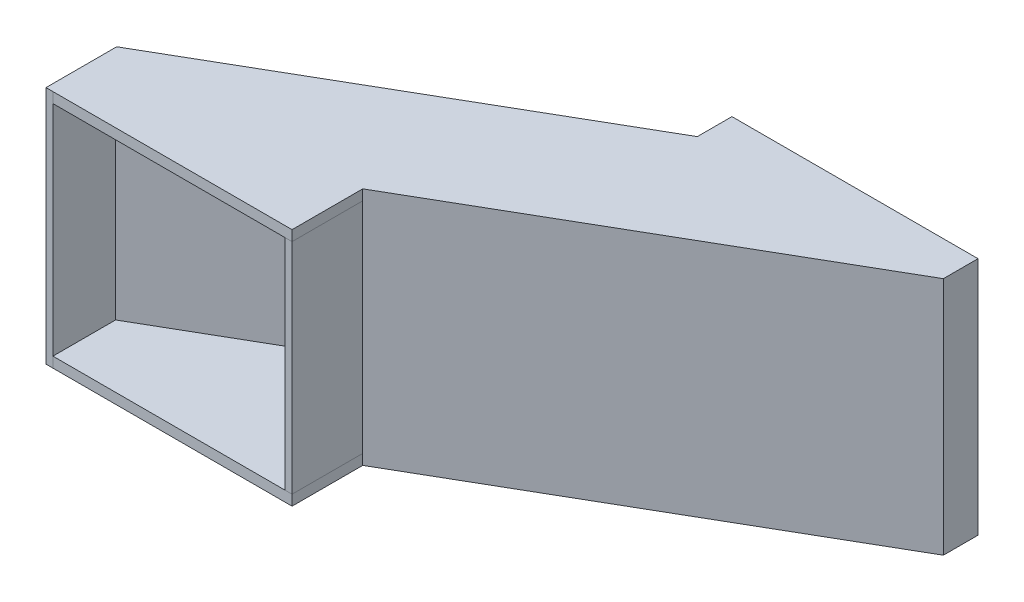
SolidWorks part; units mm, degrees
ref_plane "Front Plane" through (0, 0, 0) normal (0, 0, 1) x (1, 0, 0)
ref_plane "Top Plane" through (0, 0, 0) normal (0, 1, 0) x (1, 0, 0)
ref_plane "Right Plane" through (0, 0, 0) normal (1, 0, 0) x (0, 0, -1)
sketch "Sketch1" plane through (0, 0, 0) normal (0, 0, 1) x (1, 0, 0)
  line L0 (-32.5246, 31.5799) -> (-32.5246, -31.5799)
  line L1 (-35.5246, 34.5799) -> (35.5246, 34.5799)
  line L2 (-35.5246, 34.5799) -> (-35.5246, -34.5799)
  line L3 (-35.5246, -34.5799) -> (35.5246, -34.5799)
  line L4 (35.5246, 34.5799) -> (35.5246, -34.5799)
  line L5 (-32.5246, -31.5799) -> (32.5246, -31.5799)
  line L6 (32.5246, 31.5799) -> (32.5246, -31.5799)
  line L7 (-32.5246, 31.5799) -> (32.5246, 31.5799)
  dimension "D1" = 3
extrude "Boss-Extrude1" add sketch "Sketch1" along normal blind 10
sketch "Sketch2" plane through (0, -34.5799, 0) normal (0, -1, 0) x (1, 0, 0)
  line L0 (35.5246, 10) -> (-70.7659, 71.3669)
  line L1 (-35.5246, 10) -> (-141.8157, 71.3672)
  line L2 (-35.5246, 10) -> (35.5246, 10) construction
  line L3 (-70.7659, 91.773) -> (-141.8159, 91.773)
  line L4 (-70.7659, 71.3669) -> (-70.7659, 91.773)
  line L5 (-141.8157, 71.3672) -> (-141.8159, 91.773)
  line L6 (-35.5246, 10) -> (35.5246, 10)
  dimension "D1" = 30
  dimension "D2" = 71.05
extrude "Boss-Extrude2" add sketch "Sketch2" against normal up to surface (3 mm away) up to face at (0, -31.5799, 5)
sketch "Sketch3" plane through (0, 34.5799, 0) normal (0, 1, 0) x (1, 0, 0)
  line L0 (-35.5246, -10) -> (-141.8157, -71.3672)
  line L1 (-141.8157, -71.3672) -> (-141.8159, -91.773)
  line L2 (-141.8159, -91.773) -> (-70.7659, -91.773)
  line L3 (-70.7659, -91.773) -> (-70.7659, -71.3669)
  line L4 (-70.7659, -71.3669) -> (35.5246, -10)
  line L5 (35.5246, -10) -> (-35.5246, -10)
extrude "Boss-Extrude3" add sketch "Sketch3" against normal up to surface (3 mm away) up to face at (0, 31.5799, 5)
sketch "Sketch4" plane through (13.2113, 0, 22.8826) normal (0.5, 0, 0.866) x (0.866, 0, -0.5)
  line L0 (-96.9685, -34.5799) -> (-96.9685, 34.5799)
  line L1 (-96.9685, 34.5799) -> (25.7652, 34.5799)
  line L2 (25.7652, 34.5799) -> (25.7652, -34.5799)
  line L3 (25.7652, -34.5799) -> (-96.9685, -34.5799)
extrude "Boss-Extrude5" add sketch "Sketch4" against normal blind 3
sketch "Sketch5" plane through (-4.551, 0, -7.8826) normal (-0.5, 0, -0.866) x (-0.866, 0, 0.5)
  line L0 (35.7652, 31.5799) -> (35.7652, -31.5799)
  line L5 (35.7652, 31.5799) -> (158.4996, 31.5799)
  line L7 (35.7652, -31.5799) -> (158.4996, -31.5799)
  line L9 (158.4996, 31.5799) -> (158.4996, -31.5799)
  point P7 (157.1274, -31.5799)
  point P8 (157.1274, 31.5799)
extrude "Boss-Extrude14" add sketch "Sketch5" against normal blind 3 separate body
sketch "Sketch6" plane through (-70.7659, 0, 0) normal (1, 0, 0) x (0, 0, -1)
  line L0 (-71.3669, 31.5799) -> (-71.3669, -31.5799)
  line L2 (-91.773, -31.5799) -> (-91.773, 31.5799)
  line L4 (-91.773, 31.5799) -> (-71.3669, 31.5799)
  line L5 (-91.773, -31.5799) -> (-71.3669, -31.5799)
base flange "Base-Flange1" sketch "Sketch6" thickness 2 reverse thickness direction no parameters "D1"=0.7366
sketch "Sketch11" plane through (-141.815, 0, -0.0014) normal (-1, 0, 0) x (0, 0, 1)
  line L0 (71.3686, 34.5799) -> (71.3686, -34.5799)
  line L1 (71.3686, -34.5799) -> (91.7744, -34.5799)
  line L2 (91.7744, -34.5799) -> (91.7744, 34.5799)
  line L3 (91.7744, 34.5799) -> (71.3686, 34.5799)
base flange "Base-Flange2" sketch "Sketch11" thickness 2 reverse thickness direction no parameters "D1"=0.7366
sketch "Bend-Lines1" [suppressed] plane through (0, 0, 0) normal (0, 1, 0) x (1, 0, 0)
sketch "Bounding-Box1" [suppressed] plane through (0, 0, 0) normal (0, 1, 0) x (1, 0, 0)
sheet metal parameters "Sheet-Metal6" thickness 2 parameters "D1"=0.7366
flat pattern "Flat-Pattern6" [suppressed]
sketch "Bend-Lines2" plane through (0, 0, 0) normal (0, 1, 0) x (1, 0, 0)
sketch3d "Bounding-Box2" [suppressed]
  line L0 (71.3669, 31.5799, 0) -> (71.3669, -31.5799, 0) construction
  line L1 (91.773, 31.5799, 0) -> (91.773, -31.5799, 0) construction
  line L2 (71.3669, 31.5799, 0) -> (91.773, 31.5799, 0) construction
  line L3 (71.3669, -31.5799, 0) -> (91.773, -31.5799, 0) construction
sheet metal parameters "Sheet-Metal7" thickness 2 parameters "D1"=0.7366
flat pattern "Flat-Pattern7"
sketch "Bend-Lines3" plane through (0, 0, 0) normal (0, 1, 0) x (1, 0, 0)
sketch3d "Bounding-Box3" [suppressed]
  line L0 (-71.3686, 34.5799, 0) -> (-71.3686, -34.5799, 0) construction
  line L1 (-91.7744, 34.5799, 0) -> (-91.7744, -34.5799, 0) construction
  line L2 (-71.3686, 34.5799, 0) -> (-91.7744, 34.5799, 0) construction
  line L3 (-71.3686, -34.5799, 0) -> (-91.7744, -34.5799, 0) construction
